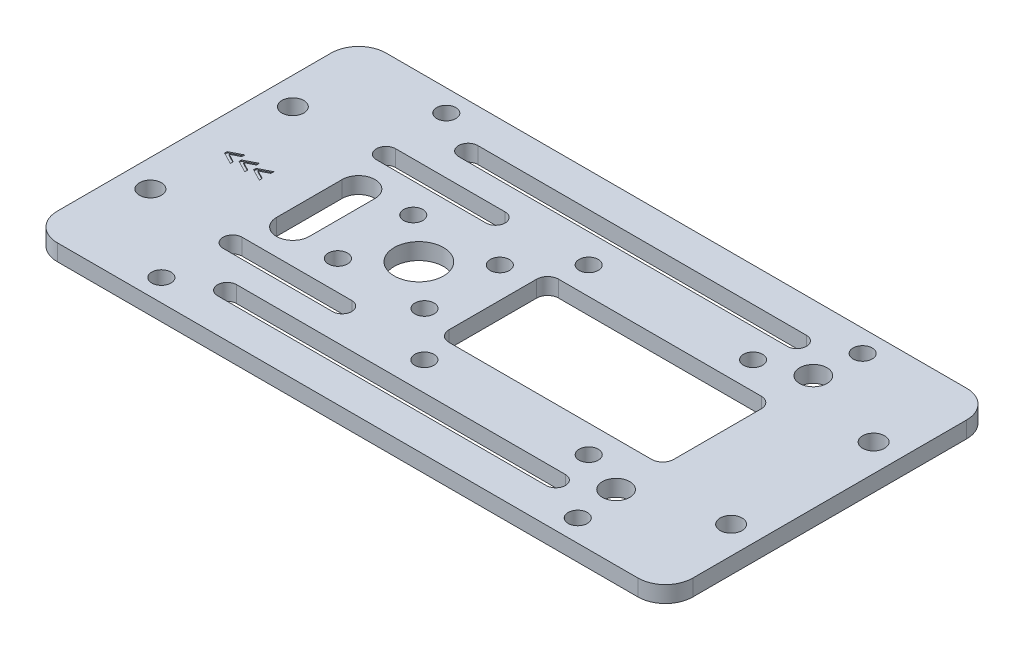
SolidWorks part; units mm, degrees
ref_plane "Front Plane" through (0, 0, 0) normal (0, 0, 1) x (1, 0, 0)
ref_plane "Top Plane" through (0, 0, 0) normal (0, 1, 0) x (1, 0, 0)
ref_plane "Right Plane" through (0, 0, 0) normal (1, 0, 0) x (0, 0, -1)
sketch "Sketch1" plane through (0, 0, 0) normal (0, 1, 0) x (1, 0, 0)
  line L0 (-58, 0) -> (58, 0) construction
  line L1 (-58, 30) -> (58, 30)
  line L2 (-58, 30) -> (-58, -30)
  line L3 (-58, -30) -> (58, -30)
  line L4 (58, 30) -> (58, -30)
  line L5 (-58, 30) -> (58, -30) construction
  line L6 (-58, -30) -> (58, 30) construction
  line L7 (0, 30) -> (0, -30) construction
  circle A0 centre (53, 13) radius 2
  circle A1 centre (53, -13) radius 2
  circle A2 centre (-53, -13) radius 2
  circle A3 centre (-53, 13) radius 2
  point P0 (0, 0)
  dimension "D4" = 4
  dimension "D1" = 60
  dimension "D2" = 116
  dimension "D3" = 13
  dimension "D5" = 53
extrude "Boss-Extrude1" add sketch "Sketch1" along normal blind 3
sketch "Sketch2" plane through (0, 3, 0) normal (0, 1, 0) x (1, 0, 0)
  line L0 (-58, 0) -> (58, 0) construction
  line L1 (-58, 30) -> (-58, -30) construction
  line L2 (58, -30) -> (58, 30) construction
  line L3 (0, 30) -> (0, -30) construction
  line L4 (58, 30) -> (-58, 30) construction
  line L5 (-58, -30) -> (58, -30) construction
  circle A0 centre (38, 26) radius 1.75
  circle A1 centre (38, -26) radius 1.75
  circle A2 centre (-38, -26) radius 1.75
  circle A3 centre (-38, 26) radius 1.75
  dimension "D1" = 3.5
  dimension "D2" = 26
  dimension "D3" = 38
extrude "Odroid-holes" cut sketch "Sketch2" against normal through all
sketch "Sketch3" plane through (0, 3, 0) normal (0, 1, 0) x (1, 0, 0)
  text T0 "<b><<<</b>"
extrude "Cut-Extrude2" cut sketch "Sketch3" against normal blind 0.2
sketch "Sketch4" plane through (0, 3, 0) normal (0, 1, 0) x (1, 0, 0)
  line L0 (58, 0) -> (-58, 0) construction
  line L1 (58, -30) -> (58, 30) construction
  line L2 (-58, 30) -> (-58, -30) construction
  line L3 (14, 30) -> (14, -30) construction
  line L4 (58, 30) -> (-58, 30) construction
  line L5 (-58, -30) -> (58, -30) construction
  line L6 (0, 30) -> (0, -30) construction
  circle A0 centre (-1, 15) radius 1.75
  circle A1 centre (29, 15) radius 1.75
  circle A2 centre (29, -15) radius 1.75
  circle A3 centre (-1, -15) radius 1.75
  dimension "D1" = 3.5
  dimension "D2" = 15
  dimension "D3" = 15
  dimension "D4" = 14
extrude "Pixhawk-PM" cut sketch "Sketch4" against normal through all
sketch "Sketch5" plane through (0, 3, 0) normal (0, 1, 0) x (1, 0, 0)
  line L0 (0, 30) -> (0, -30) construction
  line L1 (58, 30) -> (-58, 30) construction
  line L2 (-58, -30) -> (58, -30) construction
  line L3 (-17, 30) -> (-17, -30) construction
  line L4 (-58, 0) -> (58, 0) construction
  line L5 (-58, 30) -> (-58, -30) construction
  line L6 (58, -30) -> (58, 30) construction
  circle A0 centre (-9.1, 6.875) radius 1.75
  circle A1 centre (-24.9, 6.875) radius 1.75
  circle A2 centre (-24.9, -6.875) radius 1.75
  circle A3 centre (-9.1, -6.875) radius 1.75
  dimension "D1" = 3.5
  dimension "D2" = 6.875
  dimension "D3" = 7.9
  dimension "D4" = 17
extrude "BuckConverter-5A" cut sketch "Sketch5" against normal through all
sketch "Sketch6" plane through (0, 3, 0) normal (0, 1, 0) x (1, 0, 0)
  line L0 (-58, 0) -> (58, 0) construction
  line L1 (-58, 30) -> (-58, -30) construction
  line L2 (58, -30) -> (58, 30) construction
  line L3 (0, 30) -> (0, -30) construction
  line L4 (58, 30) -> (-58, 30) construction
  line L5 (-58, -30) -> (58, -30) construction
  line L6 (-30, 22) -> (30, 22) construction
  line L7 (-30, 23.75) -> (30, 23.75)
  line L8 (-30, 20.25) -> (30, 20.25)
  line L9 (-30, -22) -> (30, -22) construction
  line L10 (-30, -23.75) -> (30, -23.75)
  line L11 (-30, -20.25) -> (30, -20.25)
  line L12 (-37, 14) -> (-17, 14) construction
  line L13 (-37, 15.75) -> (-17, 15.75)
  line L14 (-37, 12.25) -> (-17, 12.25)
  line L15 (-37, -14) -> (-17, -14) construction
  line L16 (-37, -15.75) -> (-17, -15.75)
  line L17 (-37, -12.25) -> (-17, -12.25)
  line L78 (-24.9, 6.875) -> (-9.1, 6.875) construction
  line L79 (-1.5, 10) -> (35.5, 10)
  line L80 (-3.5, 8) -> (-3.5, -8)
  line L81 (-1.5, -10) -> (35.5, -10)
  line L82 (37.5, 8) -> (37.5, -8)
  line L83 (-3.5, 10) -> (37.5, -10) construction
  line L84 (-3.5, -10) -> (37.5, 10) construction
  line L85 (-9.1, 6.875) -> (-9.1, -6.875) construction
  line L86 (-9.1, -6.875) -> (-24.9, -6.875) construction
  line L87 (-24.9, -6.875) -> (-24.9, 6.875) construction
  line L88 (-17, 6.875) -> (-17, -6.875) construction
  line L89 (-34, 30) -> (-34, -30) construction
  line L90 (-34, 6) -> (-34, -6) construction
  line L91 (-31, 6) -> (-31, -6)
  line L92 (-37, 6) -> (-37, -6)
  arc A0 (-30, 23.75) -> (-30, 20.25) centre (-30, 22) ccw
  arc A1 (30, 20.25) -> (30, 23.75) centre (30, 22) ccw
  arc A2 (-30, -23.75) -> (-30, -20.25) centre (-30, -22) cw
  arc A3 (30, -20.25) -> (30, -23.75) centre (30, -22) cw
  arc A4 (-37, 15.75) -> (-37, 12.25) centre (-37, 14) ccw
  arc A5 (-17, 12.25) -> (-17, 15.75) centre (-17, 14) ccw
  arc A6 (-37, -15.75) -> (-37, -12.25) centre (-37, -14) cw
  arc A7 (-17, -12.25) -> (-17, -15.75) centre (-17, -14) cw
  arc A48 (35.5, -10) -> (37.5, -8) centre (35.5, -8) ccw
  arc A49 (35.5, 10) -> (37.5, 8) centre (35.5, 8) cw
  arc A50 (-3.5, -8) -> (-1.5, -10) centre (-1.5, -8) ccw
  arc A51 (-1.5, 10) -> (-3.5, 8) centre (-1.5, 8) ccw
  circle A52 centre (37, 18) radius 2.5
  circle A53 centre (37, -18) radius 2.5
  circle A54 centre (-17, 0) radius 4.5
  arc A55 (-31, 6) -> (-37, 6) centre (-34, 6) ccw
  arc A56 (-37, -6) -> (-31, -6) centre (-34, -6) ccw
  point P14 (0, 22)
  point P21 (0, -22)
  point P28 (-27, 14)
  point P33 (0, 0)
  point P36 (-27, -14)
  point P168 (17, 0)
  point P205 (-34, 0)
  dimension "D19" = 2
  dimension "D23" = 9
  dimension "D25" = 3
  dimension "D1" = 22
  dimension "D2" = 3.5
  dimension "D3" = 60
  dimension "D4" = 27
  dimension "D5" = 3.5
  dimension "D6" = 20
  dimension "D7" = 14
  dimension "D16" = 17
  dimension "D17" = 41
  dimension "D18" = 20
  dimension "D21" = 21
  dimension "D24" = 24
  dimension "D26" = 12
extrude "Cut-Extrude5" cut sketch "Sketch6" against normal through all contours L82 L79 L80 L81 | A54 | L7 A1 L8 A0 | L13 A5 L14 A4 | L17 A7 L16 A6 | L11 A3 L10 A2 | A52 | A53 | L91 A56 L92 A55 region at (17, 3, 0) region at (-17, 3, 0)
fillet "Fillet1" radius 5 4 edges at (58, 1.5, -30) (58, 1.5, 30) (-58, 1.5, 30) (-58, 1.5, -30)
